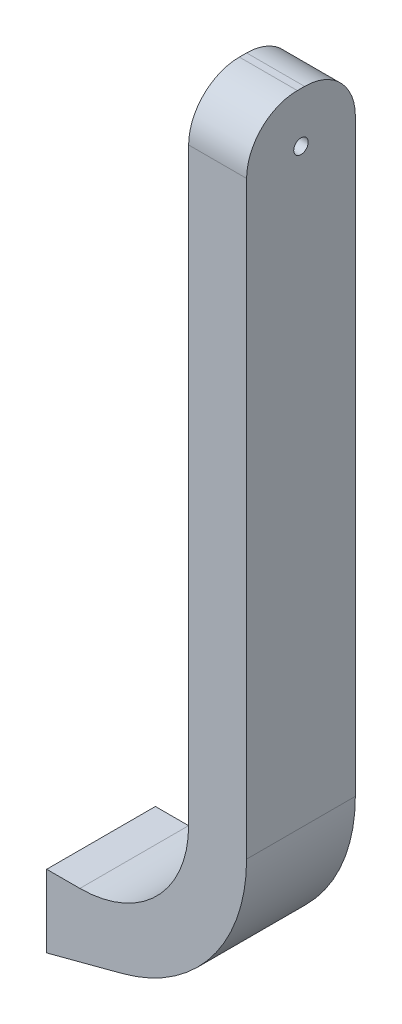
SolidWorks part; units mm, degrees
ref_plane "Front Plane" through (0, 0, 0) normal (0, 0, 1) x (1, 0, 0)
ref_plane "Top Plane" through (0, 0, 0) normal (0, 1, 0) x (1, 0, 0)
ref_plane "Right Plane" through (0, 0, 0) normal (1, 0, 0) x (0, 0, -1)
sketch "Sketch1" plane through (0, 0, 0) normal (0, 0, 1) x (1, 0, 0)
  line L0 (96.8142, 422.2536) -> (101.3962, 422.2536)
  line L1 (116.3962, 437.2536) -> (116.3962, 525.5762)
  line L9 (124.3962, 437.2536) -> (124.3962, 525.5762)
  line L10 (124.3962, 525.5762) -> (116.3962, 525.5762)
  line L11 (96.8142, 422.2536) -> (96.8142, 412.2536)
  line L12 (96.8142, 412.2536) -> (107.2717, 415.0168)
  line L14 (96.8142, 414.2536) -> (101.3962, 414.2536) construction
  arc A1 (101.3962, 422.2536) -> (116.3962, 437.2536) centre (101.3962, 437.2536) ccw
  arc A3 (107.2717, 415.0168) -> (124.3962, 437.2536) centre (101.3962, 437.2536) ccw
  arc A4 (101.3962, 414.2536) -> (124.3962, 437.2536) centre (101.3962, 437.2536) ccw construction
  dimension "D1" = 8
extrude "Boss-Extrude1" add sketch "Sketch1" against normal up to surface (15 mm away)
fillet "Fillet1" radius 7 2 edges at (120.3962, 525.5762, -15) (120.3962, 525.5762, 0)
sketch "Sketch2" plane through (116.3962, 0, 0) normal (-1, 0, 0) x (0, 0, 1)
  circle A0 centre (-7.5, 518.6762) radius 1
extrude "Cut-Extrude1" cut sketch "Sketch2" against normal up to surface (8 mm away) up to face at (124.3962, 494.2853, -7.5)
